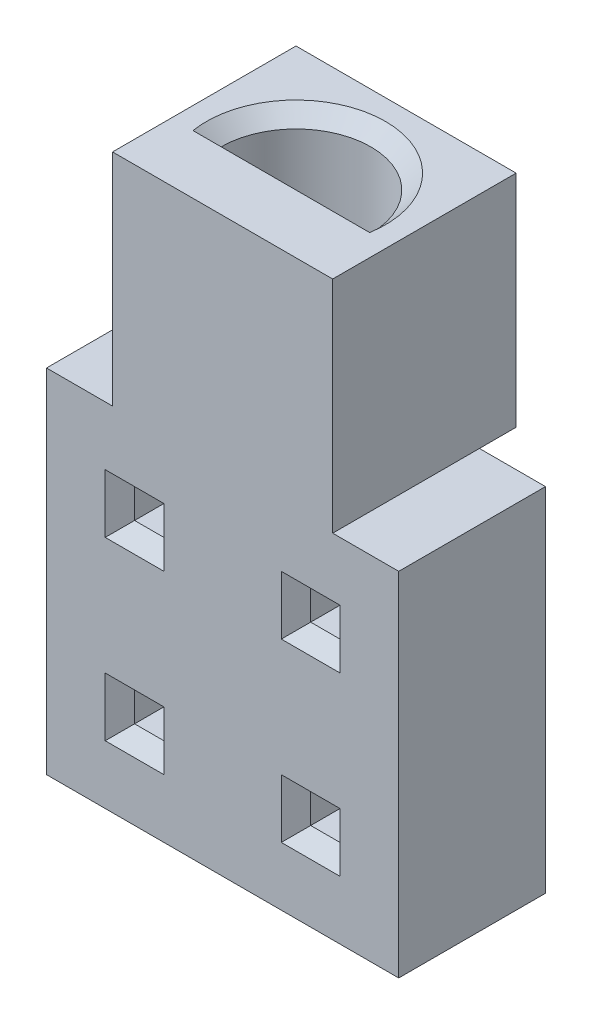
SolidWorks part; units mm, degrees
ref_plane "Ebene vorne" through (0, 0, 0) normal (0, 0, 1) x (1, 0, 0)
ref_plane "Ebene oben" through (0, 0, 0) normal (0, 1, 0) x (1, 0, 0)
ref_plane "Ebene rechts" through (0, 0, 0) normal (1, 0, 0) x (0, 0, -1)
sketch "Skizze1" plane through (0, 0, 0) normal (0, 0, 1) x (1, 0, 0)
  line L1 (-12, 12) -> (12, 12)
  line L2 (-12, 12) -> (-12, -12)
  line L3 (-12, -12) -> (12, -12)
  line L4 (12, 12) -> (12, -12)
  line L5 (-12, 12) -> (12, -12) construction
  line L6 (-12, -12) -> (12, 12) construction
  point P0 (0, 0)
  dimension "D1" = 24
  dimension "D2" = 24
extrude "Aufsatz-Linear austragen1" add sketch "Skizze1" along normal blind 5 and the other way blind 5
sketch "Skizze3" plane through (0, 12, 0) normal (0, 1, 0) x (1, 0, 0)
  line L1 (-7.5, 7.5) -> (7.5, 7.5)
  line L2 (-7.5, 7.5) -> (-7.5, -7.5)
  line L3 (-7.5, -7.5) -> (7.5, -7.5)
  line L4 (7.5, 7.5) -> (7.5, -7.5)
  line L5 (-7.5, 7.5) -> (7.5, -7.5) construction
  line L6 (-7.5, -7.5) -> (7.5, 7.5) construction
  point P0 (0, 0)
  dimension "D1" = 15
  dimension "D2" = 15
extrude "Aufsatz-Linear austragen2" add sketch "Skizze3" along normal blind 15
sketch "Skizze5" plane through (0, 27, 0) normal (0, 1, 0) x (1, 0, 0)
  line L0 (-5.1, 0) -> (5.1, 0)
  arc A0 (5.1, 0) -> (-5.1, 0) centre (0, 0) ccw
  dimension "D1" = 5.1
extrude "Schnitt-Linear austragen1" cut sketch "Skizze5" against normal blind 10
chamfer "Fase1" distance 1 angle 45 2 edges at (0, 27, -5.1) (0, 27, 0)
ref_plane "Ebene1" through (0, 0, -3) normal (0, 0, 1) x (1, 0, 0)
sketch "Skizze6" plane through (0, 0, -3) normal (0, 0, 1) x (1, 0, 0)
  line L0 (6, 12) -> (6, 7) construction
  line L1 (12, 12) -> (-12, 12) construction
  line L2 (12, 12) -> (12, -12) construction
  line L3 (12, -12) -> (-12, -12) construction
  line L4 (-12, 12) -> (-12, -12) construction
  line L5 (12, 12) -> (-12, -12) construction
  line L6 (12, -12) -> (-12, 12) construction
  line L7 (6, 7) -> (6, 5) construction
  line L8 (6, 5) -> (6, 0) construction
  line L9 (6, 0) -> (6, -5) construction
  line L10 (6, -5) -> (6, -7) construction
  line L11 (6, -7) -> (6, -12) construction
  line L12 (0, 12) -> (0, -12) construction
  line L13 (7, 7) -> (5, 7)
  line L14 (7, 7) -> (7, 5)
  line L15 (7, 5) -> (5, 5)
  line L16 (5, 7) -> (5, 5)
  line L17 (7, 7) -> (5, 5) construction
  line L18 (7, 5) -> (5, 7) construction
  line L19 (7, -5) -> (5, -5)
  line L20 (7, -5) -> (7, -7)
  line L21 (7, -7) -> (5, -7)
  line L22 (5, -5) -> (5, -7)
  line L23 (7, -5) -> (5, -7) construction
  line L24 (7, -7) -> (5, -5) construction
  line L25 (-7, -7) -> (-5, -5) construction
  line L26 (-7, -5) -> (-5, -7) construction
  line L27 (-7, 5) -> (-5, 7) construction
  line L28 (-7, 7) -> (-5, 5) construction
  line L29 (-6, -7) -> (-6, -12) construction
  line L30 (-6, -5) -> (-6, -7) construction
  line L31 (-6, 0) -> (-6, -5) construction
  line L32 (-6, 5) -> (-6, 0) construction
  line L33 (-6, 7) -> (-6, 5) construction
  line L34 (-6, 12) -> (-6, 7) construction
  line L35 (-5, -5) -> (-5, -7)
  line L36 (-7, -7) -> (-5, -7)
  line L37 (-7, -5) -> (-7, -7)
  line L38 (-7, -5) -> (-5, -5)
  line L39 (-5, 7) -> (-5, 5)
  line L40 (-7, 5) -> (-5, 5)
  line L41 (-7, 7) -> (-7, 5)
  line L42 (-7, 7) -> (-5, 7)
  line L43 (12, 6) -> (6, 6) construction
  line L44 (6, 6) -> (0, 6) construction
  point P0 (0, 0)
  point P14 (6, 6)
  point P19 (6, -6)
  point P41 (-6, -6)
  point P42 (-6, 6)
  dimension "D1" = 2
  dimension "D2" = 2
  dimension "D3" = 2
extrude "Schnitt-Linear austragen2" cut sketch "Skizze6" against normal blind 11 and the other way blind 1
mirror "Spiegeln1" about plane through (0, 0, 0) normal (0, 0, 1) of "Schnitt-Linear austragen2"
chamfer "Fase2" distance 1 angle 45 32 edges at (6, -7, -5) (7, -6, -5) (6, -5, -5) (5, -6, -5) (-7, -6, -5) (-6, -7, -5) (-5, -6, -5) (-6, -5, -5) (-7, 6, -5) (-6, 5, -5) (-5, 6, -5) (-6, 7, -5) (6, 5, -5) (5, 6, -5) (6, 7, -5) (7, 6, -5) (6, -7, 5) (7, -6, 5) (6, -5, 5) (5, -6, 5) (6, 5, 5) (7, 6, 5) (6, 7, 5) (5, 6, 5) (-6, 5, 5) (-5, 6, 5) (-6, 7, 5) (-7, 6, 5) (-6, -7, 5) (-5, -6, 5) (-6, -5, 5) (-7, -6, 5)
sketch "Skizze9" plane through (0, 0, 5) normal (0, 0, 1) x (1, 0, 0)
  line L0 (6, 12) -> (6, 7) construction
  line L1 (12, 12) -> (-12, 12) construction
  line L2 (12, 12) -> (12, -12) construction
  line L3 (12, -12) -> (-12, -12) construction
  line L4 (-12, 12) -> (-12, -12) construction
  line L5 (12, 12) -> (-12, -12) construction
  line L6 (12, -12) -> (-12, 12) construction
  line L7 (6, 7) -> (6, 5) construction
  line L8 (6, 5) -> (6, 0) construction
  line L9 (6, 0) -> (6, -5) construction
  line L10 (6, -5) -> (6, -7) construction
  line L11 (6, -7) -> (6, -12) construction
  line L12 (0, 12) -> (0, -12) construction
  line L13 (7, 7) -> (5, 7)
  line L14 (7, 7) -> (7, 5)
  line L15 (7, 5) -> (5, 5)
  line L16 (5, 7) -> (5, 5)
  line L17 (7, 7) -> (5, 5) construction
  line L18 (7, 5) -> (5, 7) construction
  line L19 (7, -5) -> (5, -5)
  line L20 (7, -5) -> (7, -7)
  line L21 (7, -7) -> (5, -7)
  line L22 (5, -5) -> (5, -7)
  line L23 (7, -5) -> (5, -7) construction
  line L24 (7, -7) -> (5, -5) construction
  line L25 (-7, -7) -> (-5, -5) construction
  line L26 (-7, -5) -> (-5, -7) construction
  line L27 (-7, 5) -> (-5, 7) construction
  line L28 (-7, 7) -> (-5, 5) construction
  line L29 (-6, -7) -> (-6, -12) construction
  line L30 (-6, -5) -> (-6, -7) construction
  line L31 (-6, 0) -> (-6, -5) construction
  line L32 (-6, 5) -> (-6, 0) construction
  line L33 (-6, 7) -> (-6, 5) construction
  line L34 (-6, 12) -> (-6, 7) construction
  line L35 (-5, -5) -> (-5, -7)
  line L36 (-7, -7) -> (-5, -7)
  line L37 (-7, -5) -> (-7, -7)
  line L38 (-7, -5) -> (-5, -5)
  line L39 (-5, 7) -> (-5, 5)
  line L40 (-7, 5) -> (-5, 5)
  line L41 (-7, 7) -> (-7, 5)
  line L42 (-7, 7) -> (-5, 7)
  line L43 (12, 6) -> (6, 6) construction
  line L44 (6, 6) -> (0, 6) construction
  line L45 (-12, 12) -> (-12, -12) construction
  point P0 (0, 0)
  point P12 (6, 6)
  point P17 (6, -6)
  point P39 (-6, -6)
  point P40 (-6, 6)
sketch "Skizze12" plane through (0, 0, 7.5) normal (0, 0, 1) x (1, 0, 0)
  line L4 (-7.5, 12) -> (7.5, 12)
  line L5 (7.5, 12) -> (7.5, 27)
  line L6 (7.5, 27) -> (-7.5, 27)
  line L7 (-7.5, 27) -> (-7.5, 12)
  line L8 (-7.5, 12) -> (7.5, 12)
  line L9 (7.5, 12) -> (7.5, 27)
  line L10 (7.5, 27) -> (-7.5, 27)
  line L11 (-7.5, 27) -> (-7.5, 12)
  dimension "D1" = 0
extrude "Schnitt-Linear austragen4" cut sketch "Skizze12" against normal up to surface (2.5 mm away) up to face at (6, -6, 5)
